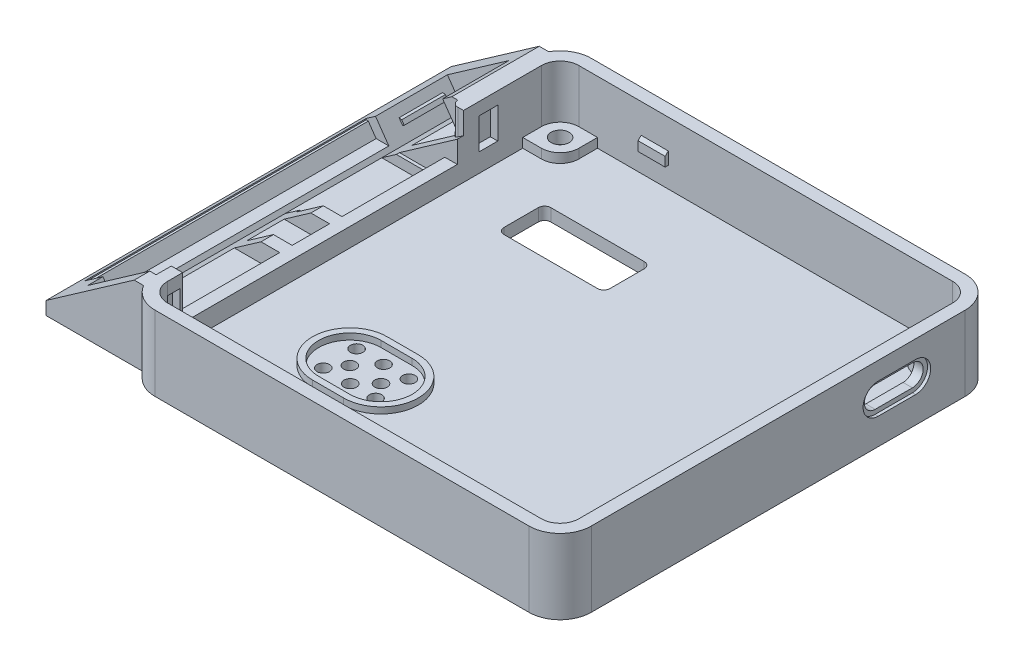
SolidWorks part; units mm, degrees
ref_plane "前视基准面" through (0, 0, 0) normal (0, 0, 1) x (1, 0, 0)
ref_plane "上视基准面" through (0, 0, 0) normal (0, 1, 0) x (1, 0, 0)
ref_plane "右视基准面" through (0, 0, 0) normal (1, 0, 0) x (0, 0, -1)
other "Configuration Table"
sketch "草图1" plane through (0, 0, 0) normal (0, 1, 0) x (1, 0, 0)
  line L1 (-30, -35) -> (30, -35)
  line L2 (-35, -30) -> (-35, 30)
  line L3 (-30, 35) -> (30, 35)
  line L4 (35, -30) -> (35, 30)
  line L5 (-35, -35) -> (35, 35) construction
  line L6 (-35, 35) -> (35, -35) construction
  line L7 (-30, -30) -> (30, -30) construction
  line L8 (-30, -30) -> (-30, 30) construction
  line L9 (-30, 30) -> (30, 30) construction
  line L10 (30, -30) -> (30, 30) construction
  line L11 (-30, -30) -> (30, 30) construction
  line L12 (-30, 30) -> (30, -30) construction
  arc A0 (-30, 35) -> (-35, 30) centre (-30, 30) ccw
  arc A1 (35, 30) -> (30, 35) centre (30, 30) ccw
  arc A2 (30, -35) -> (35, -30) centre (30, -30) ccw
  arc A3 (-35, -30) -> (-30, -35) centre (-30, -30) ccw
  point P0 (0, 0)
  point P6 (0, 0)
  dimension "D1" = 70
  dimension "D2" = 70
  dimension "D3" = 60
extrude "凸台-拉伸1" add sketch "草图1" along normal blind 2
sketch "草图2" plane through (0, 2, 0) normal (0, 1, 0) x (1, 0, 0)
  line L0 (-30, -35) -> (30, -35) construction
  line L1 (-35, 30) -> (-35, -30) construction
  line L2 (30, 35) -> (-30, 35) construction
  line L3 (35, -30) -> (35, 30) construction
  line L4 (-30, -35) -> (30, -35)
  line L5 (-35, 30) -> (-35, -30)
  line L6 (30, 35) -> (-30, 35)
  line L7 (35, -30) -> (35, 30)
  line L8 (-33, -30) -> (-33, 30)
  line L9 (-33, -33) -> (33, -33) construction
  line L10 (-33, -33) -> (-33, 33) construction
  line L11 (-33, 33) -> (33, 33) construction
  line L12 (33, -33) -> (33, 33) construction
  line L13 (-33, -33) -> (33, 33) construction
  line L14 (-33, 33) -> (33, -33) construction
  line L15 (-30, 33) -> (30, 33)
  line L16 (33, 30) -> (33, -30)
  line L17 (30, -33) -> (-30, -33)
  arc A0 (30, -35) -> (35, -30) centre (30, -30) ccw construction
  arc A1 (-35, -30) -> (-30, -35) centre (-30, -30) ccw construction
  arc A2 (-30, 35) -> (-35, 30) centre (-30, 30) ccw construction
  arc A3 (35, 30) -> (30, 35) centre (30, 30) ccw construction
  arc A4 (30, -35) -> (35, -30) centre (30, -30) ccw
  arc A5 (-35, -30) -> (-30, -35) centre (-30, -30) ccw
  arc A6 (-30, 35) -> (-35, 30) centre (-30, 30) ccw
  arc A7 (35, 30) -> (30, 35) centre (30, 30) ccw
  arc A8 (-33, 30) -> (-30, 33) centre (-30, 30) cw
  arc A9 (30, 33) -> (33, 30) centre (30, 30) cw
  arc A10 (33, -30) -> (30, -33) centre (30, -30) cw
  arc A11 (-30, -33) -> (-33, -30) centre (-30, -30) cw
  point P12 (0, 0)
  dimension "D1" = 2
extrude "凸台-拉伸2" add sketch "草图2" along normal blind 10
sketch "草图3" plane through (0, 12, 0) normal (0, 1, 0) x (1, 0, 0)
  line L1 (-33, -30) -> (-35, -30)
  line L2 (-33, -30) -> (-33, 30)
  line L3 (-33, 30) -> (-35, 30)
  line L4 (-35, -30) -> (-35, 30)
extrude "切除-拉伸1" cut sketch "草图3" against normal blind 7
sketch "草图4" plane through (0, 2, 0) normal (0, 1, 0) x (1, 0, 0)
  line L0 (-27, 30) -> (-27, 33)
  line L1 (30, 33) -> (-30, 33) construction
  line L2 (-27, 33) -> (-30, 33)
  line L3 (-30, 27) -> (-33, 27)
  line L4 (-33, -30) -> (-33, 30) construction
  line L5 (-33, 27) -> (-33, 30)
  line L6 (27, 30) -> (27, 33)
  line L7 (27, 33) -> (30, 33)
  line L8 (30, 27) -> (33, 27)
  line L9 (33, -30) -> (33, 30) construction
  line L10 (33, 27) -> (33, 30)
  line L11 (-33, -27) -> (-33, -30)
  line L12 (-30, -33) -> (30, -33) construction
  line L13 (-30, -33) -> (-27, -33)
  line L14 (33, -30) -> (33, -27)
  line L15 (-27, -30) -> (-27, -33)
  line L16 (-30, -27) -> (-33, -27)
  line L18 (33, -27) -> (30, -27)
  line L19 (27, -30) -> (27, -33)
  line L20 (27, -33) -> (30, -33)
  arc A0 (27, 30) -> (30, 27) centre (30, 30) ccw
  arc A1 (-30, 33) -> (-33, 30) centre (-30, 30) ccw
  arc A2 (-27, -30) -> (-30, -27) centre (-30, -30) ccw
  arc A4 (-30, 27) -> (-27, 30) centre (-30, 30) ccw
  arc A5 (33, 30) -> (30, 33) centre (30, 30) ccw
  arc A6 (-33, -30) -> (-30, -33) centre (-30, -30) ccw
  arc A7 (30, -33) -> (33, -30) centre (30, -30) ccw
  arc A8 (30, -27) -> (27, -30) centre (30, -30) ccw
extrude "凸台-拉伸3" add sketch "草图4" along normal blind 1.5
sketch "草图5" plane through (0, 3.5, 0) normal (0, 1, 0) x (1, 0, 0)
  circle A0 centre (30, -30) radius 1.45
  circle A1 centre (30, 30) radius 1.45
  circle A2 centre (-30, 30) radius 1.45
  circle A3 centre (-30, -30) radius 1.45
  dimension "D1" = 2.9
extrude "切除-拉伸2" cut sketch "草图5" against normal blind 2
sketch "草图6" plane through (0, 0, 0) normal (0, -1, 0) x (1, 0, 0)
  line L1 (-35, 30) -> (-50, 30)
  line L2 (-35, 30) -> (-35, -30)
  line L3 (-35, -30) -> (-50, -30)
  line L4 (-50, 30) -> (-50, -30)
  dimension "D1" = 15
extrude "凸台-拉伸4" add sketch "草图6" against normal blind 1
sketch "草图8" plane through (33, 0, 0) normal (-1, 0, 0) x (0, 0, 1)
  line L0 (-22.0249, 8.4152) -> (-16.0571, 8.4152)
  line L1 (-16.0571, 4.9395) -> (-22.0249, 4.9395)
  arc A0 (-16.0571, 8.4152) -> (-16.0571, 4.9395) centre (-16.0571, 6.6774) cw
  arc A1 (-22.0249, 4.9395) -> (-22.0249, 8.4152) centre (-22.0249, 6.6774) cw
extrude "切除-拉伸3" cut sketch "草图8" against normal blind 4
sketch "草图9" plane through (35, 0, 0) normal (1, 0, 0) x (0, 0, -1)
  line L0 (14.3193, 6.6774) -> (23.7628, 6.6774) construction
  line L1 (22.0249, 6.6774) -> (22.0249, 8.4152) construction
  line L2 (16.0571, 6.6774) -> (16.0571, 8.4152) construction
  line L3 (16.0571, 9.1152) -> (22.0249, 9.1152)
  line L4 (22.0249, 4.2395) -> (16.0571, 4.2395)
  line L5 (16.0571, 8.4152) -> (22.0249, 8.4152) construction
  arc A0 (16.0571, 8.4152) -> (16.0571, 4.9395) centre (16.0571, 6.6774) ccw construction
  arc A1 (22.0249, 4.9395) -> (22.0249, 8.4152) centre (22.0249, 6.6774) ccw construction
  arc A2 (22.0249, 9.1152) -> (22.0249, 4.2395) centre (22.0249, 6.6774) cw
  arc A3 (16.0571, 4.2395) -> (16.0571, 9.1152) centre (16.0571, 6.6774) cw
  dimension "D1" = 0.7
extrude "切除-拉伸4" cut sketch "草图9" against normal blind 0.5
sketch "草图10" plane through (0, 1, 0) normal (0, 1, 0) x (1, 0, 0)
  line L0 (-35, -30) -> (-50, -30) construction
  line L1 (-50, 30) -> (-48.7, 30)
  line L2 (-50, 30) -> (-50, -30)
  line L3 (-50, -30) -> (-48.7, -30)
  line L4 (-48.7, 30) -> (-48.7, -30)
  dimension "D1" = 1.3
extrude "凸台-拉伸5" add sketch "草图10" along normal blind 2
sketch "草图11" plane through (0, 0, 30) normal (0, 0, 1) x (1, 0, 0)
  line L0 (-43.7126, 1) -> (-38, 5)
  line L1 (-35, 1) -> (-48.7, 1) construction
  line L2 (-38, 5) -> (-35, 5)
  line L3 (-35, 5) -> (-35, 1)
  line L4 (-35, 1) -> (-43.7126, 1)
  line L5 (-48.7, 2.8) -> (-48.3604, 2.8)
  line L6 (-48.7, 3) -> (-48.7, 1) construction
  line L7 (-48.3604, 2.8) -> (-47.1, 1)
  line L8 (-47.1, 1) -> (-48.7, 1)
  line L9 (-48.7, 1) -> (-48.7, 2.8)
  dimension "D1" = 35
  dimension "D2" = 3
  dimension "D3" = 55
  dimension "D4" = 1.8
  dimension "D5" = 1.6
extrude "凸台-拉伸6" add sketch "草图11" against normal up to surface (60 mm away) up to face at (-44.5667, 1.3333, -30)
sketch "草图12" plane through (0, 0, 30) normal (0, 0, 1) x (1, 0, 0)
  line L0 (-45.0626, 1) -> (-44.6185, 0.3657)
  line L1 (-43.7126, 1) -> (-47.1, 1) construction
  line L2 (-44.6185, 0.3657) -> (-43.7126, 1)
  line L3 (-43.7126, 1) -> (-45.0626, 1)
  line L4 (-38, 5) -> (-43.7126, 1) construction
  dimension "D1" = 1.35
extrude "切除-拉伸5" cut sketch "草图12" against normal up to next and the other way through all
sketch "草图13" plane through (0, 5, 0) normal (0, 1, 0) x (1, 0, 0)
  line L0 (-35, 12) -> (-35, -30) construction
  line L1 (-44.6185, -30) -> (-44.6185, 30) construction
  line L2 (-35, -16) -> (-44.6185, -16)
  line L3 (-35, -16) -> (-35, -28)
  line L4 (-35, -28) -> (-44.6185, -28)
  line L5 (-44.6185, -16) -> (-44.6185, -28)
  line L6 (-35, -2) -> (-44.6185, -2)
  line L7 (-35, -2) -> (-35, -14)
  line L8 (-35, -14) -> (-44.6185, -14)
  line L9 (-44.6185, -2) -> (-44.6185, -14)
  line L11 (-35, 12) -> (-35, 0)
  line L12 (-35, 0) -> (-44.6185, 0)
  line L13 (-44.6185, 12) -> (-44.6185, 0)
  line L19 (-38, 30) -> (-44.6185, 30) construction
  line L20 (-35, 26) -> (-44.6185, 26) [skipped]
  line L21 (-44.6185, 26) -> (-44.6185, 14) [skipped]
  line L22 (-35, 26) -> (-35, 14) [skipped]
  line L23 (-35, 14) -> (-44.6185, 14) [skipped]
  line L24 (-44.6185, 28) -> (-35, 28)
  line L25 (-44.6185, 28) -> (-44.6185, 18.5)
  line L26 (-44.6185, 18.5) -> (-35, 18.5)
  line L27 (-35, 28) -> (-35, 18.5)
  line L28 (-38, -30) -> (-44.6185, -30) construction
  line L31 (-44.6185, 12) -> (-44.6185, 16.5)
  line L32 (-44.6185, 16.5) -> (-35, 16.5)
  line L33 (-35, 12) -> (-35, 16.5)
  line L34 (-35, 12) -> (-44.6185, 12) [skipped]
  dimension "D2" = 2
  dimension "D3" = 2
  dimension "D4" = 2
  dimension "D5" = 2
  dimension "D6" = 9.5
  dimension "D7" = 12
  dimension "D1" = 4
extrude "切除-拉伸6" cut sketch "草图13" against normal blind 3
sketch "草图14" plane through (-50, 0, 0) normal (-1, 0, 0) x (0, 0, 1)
  line L0 (-30, 12) -> (-35, 12) construction
  line L1 (-30, 0) -> (-32.5, 0)
  line L2 (-30, 0) -> (-30, 12)
  line L3 (-30, 12) -> (-32.5, 12)
  line L4 (-32.5, 0) -> (-32.5, 12)
  line L5 (35, 12) -> (30, 12) construction
  line L6 (30, 0) -> (32.5, 0)
  line L7 (30, 0) -> (30, 12)
  line L8 (30, 12) -> (32.5, 12)
  line L9 (32.5, 0) -> (32.5, 12)
extrude "凸台-拉伸7" add sketch "草图14" against normal blind 16
sketch "草图15" plane through (0, 0, 30) normal (0, 0, -1) x (-1, 0, 0)
  line L0 (35.8467, 12) -> (48.7, 3)
  line L1 (50, 12) -> (33, 12) construction
  line L2 (48.7, 3) -> (50, 3)
  line L3 (50, 3) -> (50, 12)
  line L4 (50, 12) -> (35.8467, 12)
  dimension "D1" = 145
extrude "切除-拉伸7" cut sketch "草图15" against normal mid plane 112
sketch "草图16" plane through (0, 0, -30) normal (0, 0, 1) x (1, 0, 0)
  line L0 (-50, 3) -> (-48.7, 3)
  line L1 (-48.7, 3) -> (-35.8467, 12)
  line L2 (-35.8467, 12) -> (-50, 12)
  line L3 (-50, 12) -> (-50, 3)
extrude "切除-拉伸8" cut sketch "草图16" against normal mid plane 18
sketch "草图17" plane through (0, 0, -32.5) normal (0, 0, -1) x (-1, 0, 0)
  line L0 (48.7, 3) -> (50, 2.0897)
  line L1 (50, 3) -> (50, 0) construction
  line L2 (50, 2.0897) -> (50, 3)
  line L3 (50, 3) -> (48.7, 3)
  line L4 (35.8467, 12) -> (48.7, 3) construction
extrude "切除-拉伸9" cut sketch "草图17" against normal up to next
sketch "草图18" plane through (-17.4313, 24.8945, 0) normal (-0.5736, 0.8192, 0) x (0.8192, 0.5736, 0)
  line L9 (-38.2526, -30.0551) -> (-34.6349, -30.0551)
  line L10 (-38.2526, -30.0551) -> (-38.2526, -27.5683)
  line L11 (-38.2526, -27.5683) -> (-34.6349, -27.5683)
  line L12 (-34.6349, -30.0551) -> (-34.6349, -27.5683)
  line L13 (-38.2526, 30.2595) -> (-24.2864, 30.2595)
  line L14 (-38.2526, 30.2595) -> (-38.2526, 29.1155)
  line L15 (-38.2526, 29.1155) -> (-24.2864, 29.1155)
  line L16 (-24.2864, 30.2595) -> (-24.2864, 29.1155)
extrude "凸台-拉伸11" add sketch "草图18" against normal up to surface (27.4873 mm away) up to face at (-33, 3.5, 0)
sketch "草图20" plane through (0, 5, 0) normal (0, 1, 0) x (1, 0, 0)
  line L0 (-33, 18.5) -> (-33, 17.5)
  line L1 (-33, 30) -> (-34.9, 30)
  line L2 (-33, 30) -> (-33, 18.5)
  line L4 (-34.9, 30) -> (-34.9, 18.4763)
  line L5 (-33, -30) -> (-34.8301, -30)
  line L6 (-33, -30) -> (-33, -27.5683)
  line L7 (-33, -27.5683) -> (-34.8301, -27.5683)
  line L8 (-34.8301, -30) -> (-34.8301, -27.5683)
  line L9 (-33, -30) -> (-33, 30) construction
  line L10 (-33, 17.5) -> (-33.9237, 17.5)
  arc A0 (-33.9237, 17.5) -> (-34.9, 18.4763) centre (-33.9237, 18.4763) cw
  dimension "D1" = 11.5
  dimension "D2" = 1.9
  dimension "D3" = 1
extrude "凸台-拉伸12" add sketch "草图20" along normal up to surface (7 mm away) up to face at (-7.0323, 12, 0)
sketch "草图21" plane through (0, 0, 32.5) normal (0, 0, 1) x (1, 0, 0)
  line L1 (-50, 0) -> (-18.8244, 0)
  line L2 (-50, 0) -> (-50, -21.4202)
  line L3 (-50, -21.4202) -> (-18.8244, -21.4202)
  line L4 (-18.8244, 0) -> (-18.8244, -21.4202)
extrude "切除-拉伸10" cut sketch "草图21" against normal up to surface (65 mm away) up to face at (-40.9014, 5.2179, -32.5)
sketch "草图22" plane through (-17.4313, 24.8945, 0) normal (-0.5736, 0.8192, 0) x (0.8192, 0.5736, 0)
  line L0 (-36.3395, -27.5683) -> (-36.3395, 29.1155) construction
  line L1 (-38.6019, 29.4194) -> (-36.3395, 29.4194)
  line L2 (-38.6019, 29.4194) -> (-38.6019, 17.5781)
  line L3 (-38.6019, 17.5781) -> (-36.3395, 17.5781)
  line L4 (-36.3395, 29.4194) -> (-36.3395, 17.5781)
extrude "凸台-拉伸14" add sketch "草图22" against normal up to surface (4.9454 mm away) up to face at (-9.7259, 0, 0)
sketch "草图23" plane through (0, 0, -16.5) normal (0, 0, 1) x (1, 0, 0)
  line L0 (-38, 5) -> (-33, 8.501)
  line L2 (-33, 8.501) -> (-33, 5)
  line L3 (-33, 5) -> (-38, 5)
  line L4 (-38, 5) -> (-42.2844, 2) construction
extrude "凸台-拉伸15" add sketch "草图23" against normal blind 2
sketch "草图24" plane through (-17.4313, 24.8945, 0) normal (-0.5736, 0.8192, 0) x (0.8192, 0.5736, 0)
  line L1 (-24.2864, 30) -> (-21.7055, 30)
  line L2 (-24.2864, 30) -> (-24.2864, 18.4763)
  line L3 (-24.2864, 18.4763) -> (-21.7055, 18.4763)
  line L4 (-21.7055, 30) -> (-21.7055, 18.4763)
extrude "凸台-拉伸16" add sketch "草图24" against normal up to surface (3.8555 mm away) up to face at (-33, 6.643, -0.9188)
sketch "草图25" plane through (0, 0, -35) normal (0, 0, -1) x (-1, 0, 0)
  line L0 (-30, 12) -> (30, 12) construction
  line L1 (29.1973, 12) -> (38.3709, 12)
  line L2 (29.1973, 12) -> (29.1973, 15.5813)
  line L3 (29.1973, 15.5813) -> (38.3709, 15.5813)
  line L4 (38.3709, 12) -> (38.3709, 15.5813)
extrude "切除-拉伸11" cut sketch "草图25" against normal blind 18
sketch "草图26" plane through (0, 0, -29.1155) normal (0, 0, 1) x (1, 0, 0)
  line L0 (-38, 5) -> (-34.9, 7.1706)
  line L1 (-34.9, 5) -> (-34.9, 7.5003) construction
  line L2 (-34.9, 7.1706) -> (-34.9, 5)
  line L3 (-34.9, 5) -> (-38, 5)
  line L4 (-38, 5) -> (-42.2844, 2) construction
extrude "凸台-拉伸17" add sketch "草图26" along normal up to surface (1.1155 mm away) up to face at (-37.5711, 3.5, -28)
sketch "草图27" plane through (33, 0, 0) normal (-1, 0, 0) x (0, 0, 1)
  line L0 (-39.7195, 10) -> (41.5559, 10) construction
  line L1 (30, 12) -> (-30, 12) construction
  line L2 (-39.7195, 5) -> (41.5559, 5) construction
  line L3 (30, 12) -> (30, 3.5) construction
  line L8 (-12.5, 10) -> (-9.5, 10)
  line L9 (-12.5, 10) -> (-12.5, 5)
  line L10 (-12.5, 5) -> (-9.5, 5)
  line L11 (-9.5, 10) -> (-9.5, 5)
  line L12 (4, 10) -> (7, 10)
  line L13 (4, 10) -> (4, 5)
  line L14 (4, 5) -> (7, 5)
  line L15 (7, 10) -> (7, 5)
  dimension "D1" = 2
  dimension "D2" = 5
  dimension "D3" = 3
  dimension "D4" = 3
  dimension "D5" = 13.5
  dimension "D6" = 23
extrude "切除-拉伸12" cut sketch "草图27" against normal blind 1.2
sketch "草图29" plane through (-33, 0, 0) normal (1, 0, 0) x (0, 0, -1)
  line L0 (-46.2025, 10) -> (42.2339, 10) construction
  line L1 (-46.2025, 5) -> (42.2339, 5) construction
  line L2 (17.5, 12) -> (30, 12) construction
  line L3 (30, 12) -> (30, 3.5) construction
  line L4 (20, 10) -> (23, 10)
  line L5 (20, 10) -> (20, 5)
  line L6 (20, 5) -> (23, 5)
  line L7 (23, 10) -> (23, 5)
  line L9 (-30, 10) -> (-28, 10)
  line L10 (-30, 10) -> (-30, 5)
  line L11 (-30, 5) -> (-28, 5)
  line L12 (-28, 10) -> (-28, 5)
  line L13 (-30, 12) -> (-30, 3.5) construction
  dimension "D1" = 2
  dimension "D2" = 5
  dimension "D3" = 3
  dimension "D4" = 7
  dimension "D5" = 2
extrude "切除-拉伸13" cut sketch "草图29" against normal blind 1.2
sketch "草图30" plane through (0, 2, 0) normal (0, 1, 0) x (1, 0, 0)
  line L0 (-44.6185, -27.5683) -> (-44.6185, 29.1155) construction
  line L1 (-37, 16) -> (-44.6185, 16)
  line L2 (-37, 16) -> (-37, 0.5)
  line L3 (-37, 0.5) -> (-44.6185, 0.5)
  line L4 (-44.6185, 16) -> (-44.6185, 0.5)
  line L5 (-33, 16.5) -> (-42.2844, 16.5) construction
  line L6 (-35, 0) -> (-35, 16.5) construction
  line L7 (-42.2844, 0) -> (-38, 0) construction
  dimension "D1" = 0.5
  dimension "D2" = 2
  dimension "D3" = 0.5
extrude "切除-拉伸14" cut sketch "草图30" against normal up to vertex (1.6343 mm away) up to point (-44.6185, 0.3657, 27.5683)
ref_plane "基准面1" through (0, 0, 8) normal (0, 0, 1) x (1, 0, 0)
sketch "草图31" plane through (0, 0, 8) normal (0, 0, 1) x (1, 0, 0)
  line L0 (-42.2844, 2) -> (-38, 5)
  line L1 (-38, 5) -> (-35, 5)
  line L2 (-35, 5) -> (-35, 2)
  line L3 (-35, 2) -> (-42.2844, 2)
extrude "凸台-拉伸18" add sketch "草图31" along normal blind 2
sketch "草图32" plane through (0, 0, 10) normal (0, 0, 1) x (1, 0, 0)
  line L0 (-38, 5) -> (-35, 5)
  line L1 (-35, 5) -> (-35, 2)
  line L2 (-35, 2) -> (-42.2844, 2)
  line L3 (-42.2844, 2) -> (-38, 5)
extrude "切除-拉伸15" cut sketch "草图32" along normal blind 7
sketch "草图33" plane through (0, 0, -33) normal (0, 0, 1) x (1, 0, 0)
  line L0 (-30, 12) -> (-30, 3.5) construction
  line L1 (-20, 7.3) -> (-15.6463, 7.3)
  line L2 (-20, 7.3) -> (-20, 5.3)
  line L3 (-20, 5.3) -> (-15.6463, 5.3)
  line L4 (-15.6463, 7.3) -> (-15.6463, 5.3)
  line L5 (30, 12) -> (-30, 12) construction
  dimension "D1" = 2
  dimension "D2" = 10
  dimension "D3" = 4.7
extrude "凸台-拉伸19" add sketch "草图33" along normal blind 0.5
chamfer "倒角1" distance 0.5 angle 45 1 edges at (-17.8231, 7.3, -32.5)
sketch "草图34" plane through (0, 0, 33) normal (0, 0, -1) x (-1, 0, 0)
  line L0 (30, 12) -> (30, 3.5) construction
  line L1 (14.2735, 7.3) -> (20, 7.3)
  line L2 (14.2735, 7.3) -> (14.2735, 5.3)
  line L3 (14.2735, 5.3) -> (20, 5.3)
  line L4 (20, 7.3) -> (20, 5.3)
  line L5 (30, 12) -> (-30, 12) construction
  dimension "D1" = 2
  dimension "D2" = 10
  dimension "D3" = 4.7
extrude "凸台-拉伸20" add sketch "草图34" along normal blind 0.5
chamfer "倒角2" distance 0.5 angle 45 1 edges at (-17.1368, 7.3, 32.5)
sketch "草图35" plane through (0, 2, 0) normal (0, 1, 0) x (1, 0, 0)
  line L0 (30, 33) -> (-30, 33) construction
  line L1 (-6.5, 21) -> (-23.5, 21)
  line L2 (-6.5, 21) -> (-6.5, 13.5)
  line L3 (-6.5, 13.5) -> (-23.5, 13.5)
  line L4 (-23.5, 21) -> (-23.5, 13.5)
  line L5 (-33, 17.5) -> (-33, 30) construction
  dimension "D1" = 7.5
  dimension "D2" = 17
  dimension "D3" = 12
  dimension "D4" = 9.5
extrude "切除-拉伸16" cut sketch "草图35" against normal up to surface (2 mm away) up to face at (-9.7259, 0, 0)
sketch "草图36" plane through (0, 2, 0) normal (0, 1, 0) x (1, 0, 0)
  line L0 (-16.6713, -17.0728) -> (-11.6713, -17.0728) construction
  line L1 (-16.6713, -12.0728) -> (-11.6713, -12.0728)
  line L2 (-16.6713, -22.0728) -> (-11.6713, -22.0728)
  line L3 (-16.6713, -17.0728) -> (-11.6713, -17.0728) construction
  line L4 (-16.6713, -11.0728) -> (-11.6713, -11.0728)
  line L5 (-16.6713, -23.0728) -> (-11.6713, -23.0728)
  arc A0 (-16.6713, -12.0728) -> (-16.6713, -22.0728) centre (-16.6713, -17.0728) ccw
  arc A1 (-11.6713, -22.0728) -> (-11.6713, -12.0728) centre (-11.6713, -17.0728) ccw
  arc A2 (-16.6713, -11.0728) -> (-16.6713, -23.0728) centre (-16.6713, -17.0728) ccw
  arc A3 (-11.6713, -23.0728) -> (-11.6713, -11.0728) centre (-11.6713, -17.0728) ccw
  point P2 (-14.1713, -17.0728)
  point P9 (-14.1713, -17.0728)
  dimension "D1" = 10
  dimension "D3" = 1
  dimension "D2" = 5
extrude "凸台-拉伸21" add sketch "草图36" along normal blind 1
sketch "草图37" plane through (0, 2, 0) normal (0, 1, 0) x (1, 0, 0)
  circle A0 centre (-11.6713, -17.0728) radius 1
  circle A1 centre (-16.6713, -17.0728) radius 1
  circle A2 centre (-14.1255, -14.2044) radius 1
  circle A3 centre (-18.4511, -14.2044) radius 1
  circle A4 centre (-10.0565, -14.2044) radius 1
  circle A5 centre (-18.4511, -19.5564) radius 1
  circle A6 centre (-14.1255, -19.5564) radius 1
  circle A7 centre (-10.0565, -19.5564) radius 1
  dimension "D1" = 2
extrude "切除-拉伸17" cut sketch "草图37" against normal up to surface (2 mm away) up to face at (-15, 0, -17.25)
fillet "圆角1" radius 1 4 edges at (-6.5, 1, -13.5) (-23.5, 1, -13.5) (-23.5, 1, -21) (-6.5, 1, -21)
sketch "草图38" plane through (-29.7676, -20.8435, 0) normal (0.8192, 0.5736, 0) x (0, 0, -1)
  line L0 (32.5, 19.691) -> (32.5, 28.6788) construction
  line L1 (20.5, 28.8906) -> (27.5, 28.8906)
  line L2 (20.5, 28.8906) -> (20.5, 27.8906)
  line L3 (20.5, 27.8906) -> (27.5, 27.8906)
  line L4 (27.5, 28.8906) -> (27.5, 27.8906)
  line L5 (17.5781, 30.3906) -> (29.1155, 30.3906) construction
  dimension "D1" = 1
  dimension "D2" = 7
  dimension "D3" = 5
  dimension "D4" = 1.5
extrude "凸台-拉伸22" add sketch "草图38" along normal blind 0.3
sketch "草图39" plane through (-19.8943, -13.9301, 0) normal (-0.8192, -0.5736, 0) x (0, 0, 1)
  line L0 (-32.5, 19.691) -> (-32.5, 29.5208) construction
  line L1 (-27.5, 28.8906) -> (-20.5, 28.8906)
  line L2 (-27.5, 28.8906) -> (-27.5, 27.8906)
  line L3 (-27.5, 27.8906) -> (-20.5, 27.8906)
  line L4 (-20.5, 28.8906) -> (-20.5, 27.8906)
  line L5 (-29.1155, 30.3906) -> (-18.4763, 30.3906) construction
  dimension "D1" = 1
  dimension "D2" = 5
  dimension "D3" = 7
  dimension "D4" = 1.5
extrude "凸台-拉伸23" add sketch "草图39" along normal blind 0.3
chamfer "倒角3" distance 0.3 angle 45 2 edges at (-36.711, 9.5636, -24) (-46.0928, 2.9944, -24)
